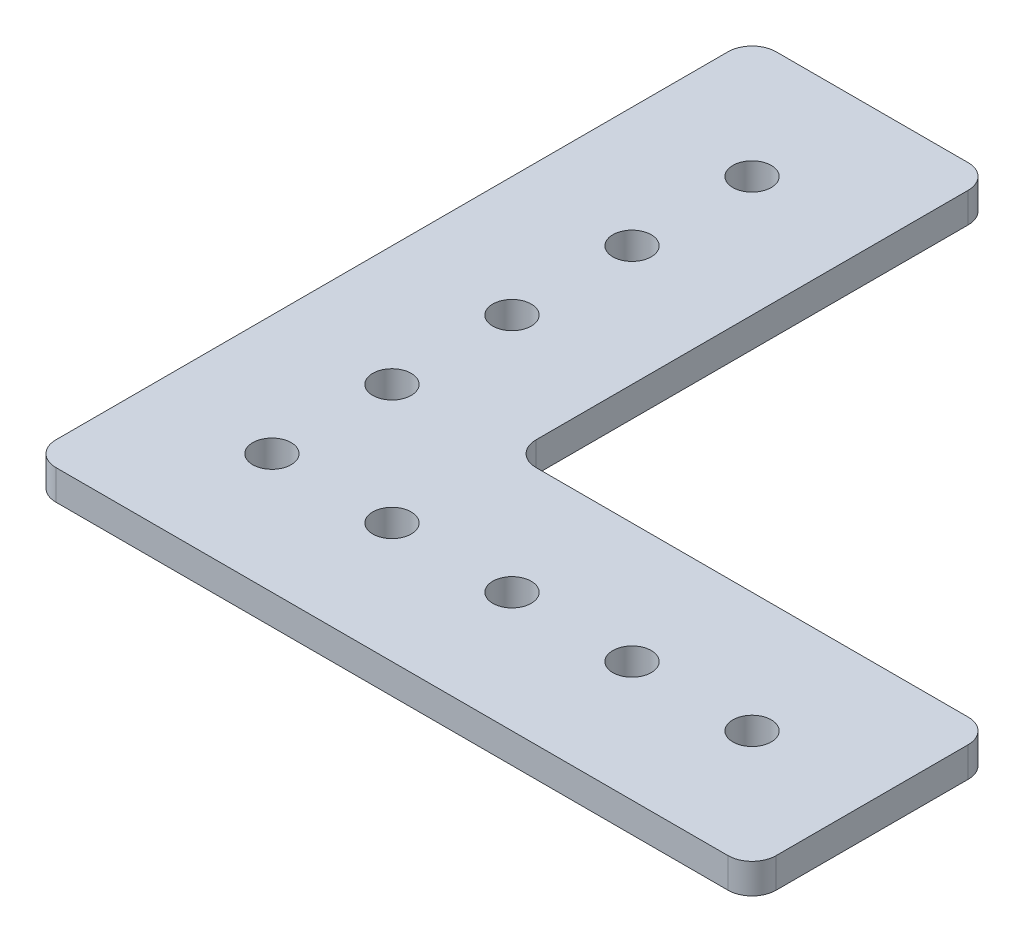
SolidWorks part; units mm, degrees
material "1060 Alloy"
ref_plane "Front Plane" through (0, 0, 0) normal (0, 0, 1) x (1, 0, 0)
ref_plane "Top Plane" through (0, 0, 0) normal (0, 1, 0) x (1, 0, 0)
ref_plane "Right Plane" through (0, 0, 0) normal (1, 0, 0) x (0, 0, -1)
sketch "Sketch1" plane through (0, 0, 0) normal (0, 1, 0) x (1, 0, 0)
  line L1 (2.54, 0) -> (25.4, 0)
  line L2 (0, 2.54) -> (0, 73.66)
  line L3 (2.54, 76.2) -> (22.86, 76.2)
  line L4 (25.4, 27.94) -> (25.4, 73.66)
  line L5 (0, 0) -> (73.66, 0)
  line L6 (0, 0) -> (0, 25.4)
  line L7 (27.94, 25.4) -> (73.66, 25.4)
  line L8 (76.2, 2.54) -> (76.2, 22.86)
  circle A0 centre (12.7, 12.7) radius 2.032
  circle A1 centre (25.4, 12.7) radius 2.032
  circle A2 centre (38.1, 12.7) radius 2.032
  circle A3 centre (50.8, 12.7) radius 2.032
  circle A4 centre (12.7, 25.4) radius 2.032
  circle A5 centre (12.7, 38.1) radius 2.032
  circle A6 centre (12.7, 50.8) radius 2.032
  arc A7 (0, 2.54) -> (2.54, 0) centre (2.54, 2.54) ccw
  arc A8 (73.66, 0) -> (76.2, 2.54) centre (73.66, 2.54) ccw
  arc A9 (76.2, 22.86) -> (73.66, 25.4) centre (73.66, 22.86) ccw
  arc A10 (27.94, 25.4) -> (25.4, 27.94) centre (27.94, 27.94) cw
  arc A11 (25.4, 73.66) -> (22.86, 76.2) centre (22.86, 73.66) ccw
  arc A12 (0, 73.66) -> (2.54, 76.2) centre (2.54, 73.66) cw
  circle A13 centre (12.7, 63.5) radius 2.032
  circle A14 centre (63.5, 12.7) radius 2.032
  point P28 (76.2, 0)
  point P31 (76.2, 25.4)
  point P36 (25.4, 76.2)
  point P39 (0, 76.2)
  dimension "D5" = 4.064
  dimension "D6" = 4.064
  dimension "D7" = 4.064
  dimension "D8" = 4.064
  dimension "D9" = 12.7
  dimension "D10" = 12.7
  dimension "D11" = 12.7
  dimension "D12" = 12.7
  dimension "D13" = 12.7
  dimension "D14" = 12.7
  dimension "D15" = 12.7
  dimension "D16" = 12.7
  dimension "D17" = 4.064
  dimension "D18" = 12.7
  dimension "D19" = 4.064
  dimension "D20" = 12.7
  dimension "D21" = 4.064
  dimension "D22" = 12.7
  dimension "D23" = 12.7
  dimension "D24" = 12.7
  dimension "D25" = 12.7
  dimension "D26" = 2.54
  dimension "D27" = 4.064
  dimension "D29" = 4.064
  dimension "D1" = 76.2
  dimension "D2" = 76.2
  dimension "D3" = 25.4
  dimension "D4" = 25.4
  dimension "D28" = 12.7
  dimension "D30" = 12.7
extrude "Boss-Extrude1" add sketch "Sketch1" along normal blind 3.175 contours A12 L2 A7 L1 L5 A8 L8 A9 L7 A10 L4 A11 L3 A6 A5 A4 A3 A2 A1 A0 region at (1.5059, 0, -1.5059)
